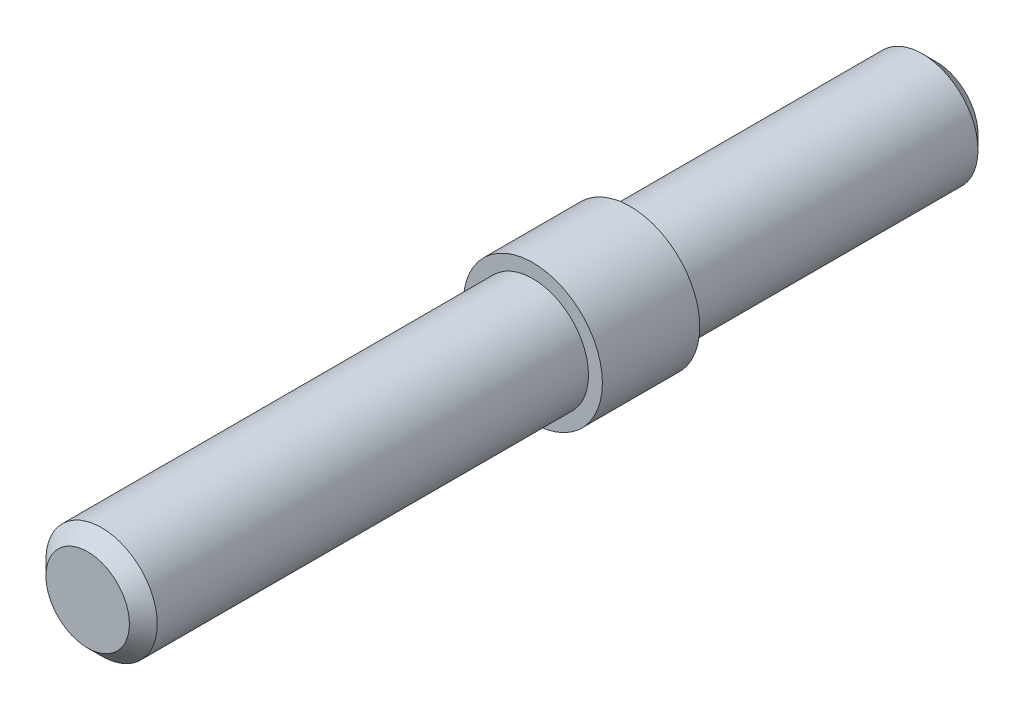
SolidWorks part; units mm, degrees
ref_plane "前视基准面" through (0, 0, 0) normal (0, 0, 1) x (1, 0, 0)
ref_plane "上视基准面" through (0, 0, 0) normal (0, 1, 0) x (1, 0, 0)
ref_plane "右视基准面" through (0, 0, 0) normal (1, 0, 0) x (0, 0, -1)
sketch "草图1" plane through (0, 0, 0) normal (0, 0, 1) x (1, 0, 0)
  circle A0 centre (0, 0) radius 4
  dimension "D1" = 8
extrude "凸台-拉伸1" add sketch "草图1" along normal blind 45 and the other way blind 16
ref_axis "基准轴1" through (0, 0, -16) along (0, 0, 1)
sketch "草图2" plane through (0, 0, -16) normal (0, 0, -1) x (-1, 0, 0)
  line L0 (0, 0) -> (11.727, 0)
ref_plane "基准面1" through (0, 0, 0) normal (0, 1, 0) x (1, 0, 0)
sketch "草图3" plane through (0, 0, 0) normal (0, 1, 0) x (1, 0, 0)
  line L1 (4, -45) -> (4, 16) construction
  circle A1 centre (0, -17.5) radius 1.5
  dimension "D1" = 17.5
  dimension "D3" = 3
  dimension "D4" = 4
extrude "切除-拉伸1" cut sketch "草图3" against normal blind 10 contours A1
chamfer "倒角1" distance 1 angle 45 1 edges at (4, 0, 45)
sketch "草图5" plane through (0, 0, 45) normal (0, 0, 1) x (1, 0, 0)
  circle A0 centre (0, 0) radius 5
  dimension "D1" = 10
extrude "凸台-拉伸3" add sketch "草图5" along normal blind 7 from offset 39 offset against normal yes
sketch "草图8" plane through (0, 0, 0) normal (0, 1, 0) x (1, 0, 0)
  line L0 (0, 16) -> (0, -45) construction
  line L1 (4, 16) -> (-4, 16) construction
  circle A0 centre (0, 11) radius 1.5
  dimension "D1" = 5
extrude "切除-拉伸2" cut sketch "草图8" against normal blind 10
chamfer "倒角2" distance 1 angle 45 1 edges at (4, 0, -16)
